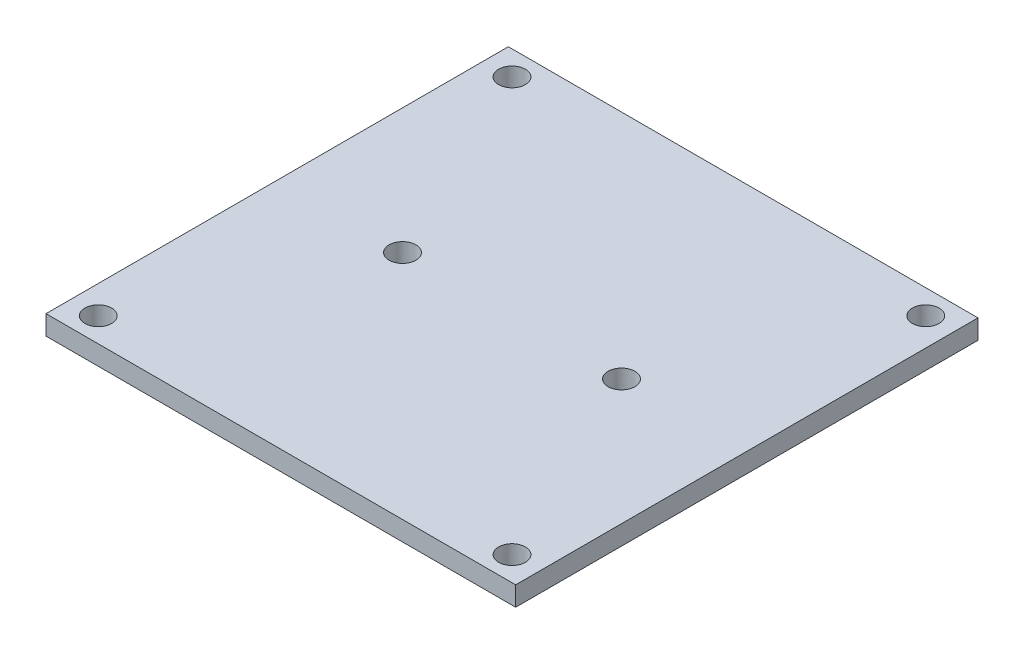
SolidWorks part; units mm, degrees
material "FR4_stuffedProtoboard"
ref_plane "Front Plane" through (0, 0, 0) normal (0, 0, 1) x (1, 0, 0)
ref_plane "Top Plane" through (0, 0, 0) normal (0, 1, 0) x (1, 0, 0)
ref_plane "Right Plane" through (0, 0, 0) normal (1, 0, 0) x (0, 0, -1)
sketch "Sketch1" plane through (0, 0, 0) normal (0, 1, 0) x (1, 0, 0)
  line L1 (-19.3, -19) -> (19.3, -19)
  line L2 (-19.3, -19) -> (-19.3, 19)
  line L3 (-19.3, 19) -> (19.3, 19)
  line L4 (19.3, -19) -> (19.3, 19)
  line L5 (-19.3, -19) -> (19.3, 19) construction
  line L6 (-19.3, 19) -> (19.3, -19) construction
  line L16 (-7.9, 0) -> (7.9, 0) construction
  line L17 (15.9, 17) -> (-15.9, 17) construction
  line L18 (17, 15.9) -> (17, -15.9) construction
  line L23 (3.5, 3.5) -> (-3.5, 3.5)
  line L24 (3.5, 3.5) -> (3.5, -3.5)
  line L29 (3.5, -3.5) -> (-3.5, -3.5)
  line L30 (-3.5, 3.5) -> (-3.5, -3.5)
  line L31 (3.5, 3.5) -> (-3.5, -3.5) construction
  line L32 (3.5, -3.5) -> (-3.5, 3.5) construction
  circle A8 centre (-17, 17) radius 1.1
  circle A9 centre (17, 17) radius 1.1
  circle A10 centre (17, -17) radius 1.1
  circle A11 centre (-17, -17) radius 1.1
  circle A13 centre (9, 0) radius 1.1
  circle A14 centre (-9, 0) radius 1.1
  point P0 (15.9, 17)
  point P5 (15.9, -17)
  point P7 (-15.9, 17)
  point P10 (0, 0)
  point P17 (17, 18.1)
  point P18 (18.1, 17)
  point P19 (17, -18.1)
  point P20 (17, 15.9)
  point P24 (17, -15.9)
  point P32 (9, -1.1)
  point P35 (10.1, 0)
  point P37 (7.9, 0)
  point P38 (-7.9, 0)
  point P39 (-10.1, 0)
  point P40 (9, 1.1)
  point P44 (0, 17)
  point P45 (17, 0)
  dimension "D3" = 31.8
  dimension "D6" = 17.9
  dimension "D7" = 2.2
  dimension "D10" = 2.2
  dimension "D1" = 38
  dimension "D2" = 38.6
  dimension "D4" = 7
  dimension "D5" = 15.8
  dimension "D11" = 31.8
extrude "Camera Board Base" add sketch "Sketch1" against normal blind 1.6 contours L1 L4 L3 L2 A9 A8 A10 A11 | L23 L30 L29 L24 region at (-18.7583, 0, 0) region at (0, 0, 0)
extrude "Sensor" add sketch "Sketch1<5>" against normal blind 2.6 contours L23 L30 L29 L24 region at (0, 0, 0)
sketch "Sketch1<5>" plane through (0, 0, 0) normal (0, 1, 0) x (1, 0, 0) same geometry as "Sketch1"
sketch "Footprint" plane through (0, 0, 0) normal (0, 1, 0) x (1, 0, 0)
  line L0 (-7.3, 2.3) -> (-8.8075, 2.3)
  line L1 (-7.3, 7.7) -> (7.3, 7.7)
  line L2 (-7.3, 7.7) -> (-7.3, -7.7)
  line L3 (-7.3, -7.7) -> (7.3, -7.7)
  line L4 (7.3, 7.7) -> (7.3, -7.7)
  line L5 (-7.3, 7.7) -> (7.3, -7.7) construction
  line L6 (-7.3, -7.7) -> (7.3, 7.7) construction
  line L7 (-6.3, 6.7) -> (6.3, 6.7)
  line L8 (-6.3, 6.7) -> (-6.3, -6.7)
  line L9 (-6.3, -6.7) -> (6.3, -6.7)
  line L10 (6.3, 6.7) -> (6.3, -6.7)
  line L11 (-6.3, 6.7) -> (6.3, -6.7) construction
  line L12 (-6.3, -6.7) -> (6.3, 6.7) construction
  line L13 (-8.8075, -2.3) -> (-7.3, -2.3)
  line L14 (7.3, 2.3) -> (8.8075, 2.3)
  line L15 (7.3, -2.3) -> (8.8075, -2.3)
  line L16 (-11.1, 0) -> (11.1, 0) construction
  circle A0 centre (-9, 0) radius 1
  circle A1 centre (-9, 0) radius 1.1 construction
  circle A2 centre (9, 0) radius 1
  arc A3 (8.8075, 2.3) -> (8.8075, -2.3) centre (8.8, 0) cw
  arc A4 (-8.8075, 2.3) -> (-8.8075, -2.3) centre (-8.8, 0) ccw
  point P0 (0, 0)
  point P7 (0, 0)
  dimension "D7" = 2
  dimension "D1" = 14.6
  dimension "D2" = 15.4
  dimension "D3" = 1
  dimension "D4" = 1
  dimension "D5" = 1
  dimension "D6" = 1
  dimension "D8" = 18
  dimension "D9" = 4.6
  dimension "D10" = 22.2
  dimension "D11" = 3.8
